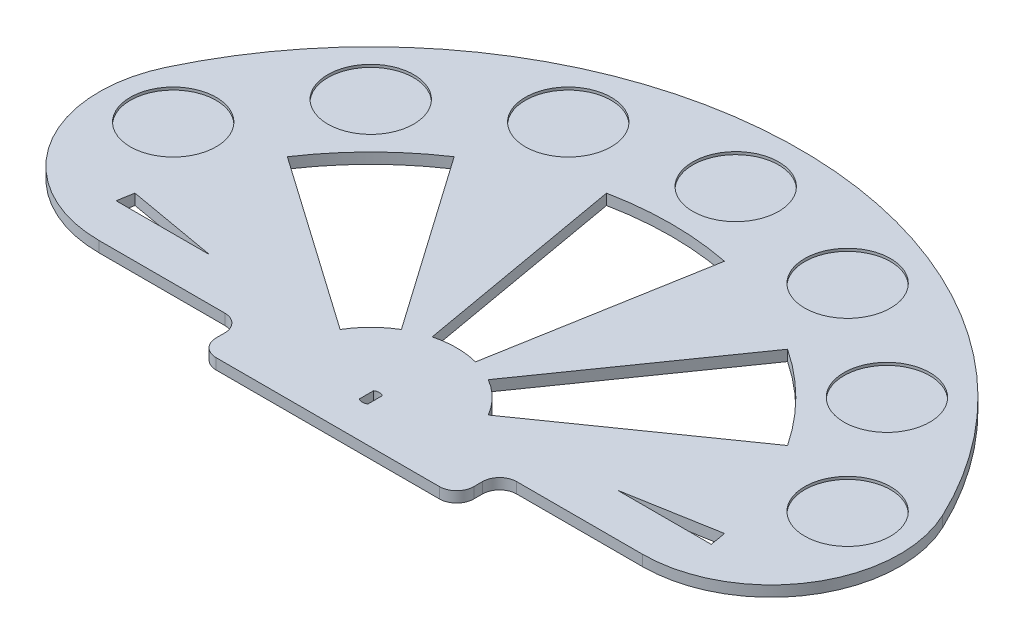
SolidWorks part; units mm, degrees
ref_plane "Front Plane" through (0, 0, 0) normal (0, 0, 1) x (1, 0, 0)
ref_plane "Top Plane" through (0, 0, 0) normal (0, 1, 0) x (1, 0, 0)
ref_plane "Right Plane" through (0, 0, 0) normal (1, 0, 0) x (0, 0, -1)
sketch "Sketch1" plane through (0, 0, 0) normal (0, 1, 0) x (1, 0, 0)
  line L0 (-80.3219, 0) -> (-43.18, 0)
  line L1 (43.18, 0) -> (80.3219, 0)
  line L3 (-38.1, -5.08) -> (-38.1, -7.62)
  line L4 (-33.02, -12.7) -> (33.02, -12.7)
  line L5 (38.1, -5.08) -> (38.1, -7.62)
  line L6 (-1.28, 2.1475) -> (-1.28, -2.1475)
  line L7 (1.28, 2.1475) -> (1.28, -2.1475)
  line L8 (-87.9882, 12.7) -> (87.9882, 12.7) construction
  line L11 (0, 88.9) -> (0, 25.4) construction
  line L12 (-17.4437, 87.1718) -> (-6.4069, 24.5787)
  line L13 (17.4437, 87.1718) -> (6.4069, 24.5787)
  line L14 (-11.9253, 55.8753) -> (11.9253, 55.8753) construction
  line L15 (73.9744, 49.3052) -> (21.9101, 12.8494)
  line L16 (49.3052, 73.9744) -> (12.8494, 21.9101)
  line L18 (87.1718, 17.4437) -> (60.2688, 12.7)
  line L25 (-87.1718, 17.4437) -> (-60.2688, 12.7)
  line L27 (-49.3052, 73.9744) -> (-12.8494, 21.9101)
  line L28 (-73.9744, 49.3052) -> (-21.9101, 12.8494)
  line L29 (-73.9744, -49.3052) -> (-21.9101, -12.8494) [skipped]
  line L30 (-49.3052, -73.9744) -> (-12.8494, -21.9101) [skipped]
  line L31 (-17.4437, -87.1718) -> (-6.4069, -24.5787) [skipped]
  line L32 (17.4437, -87.1718) -> (6.4069, -24.5787) [skipped]
  line L33 (49.3052, -73.9744) -> (12.8494, -21.9101) [skipped]
  line L34 (73.9744, -49.3052) -> (21.9101, -12.8494) [skipped]
  line L35 (87.1718, -17.4437) -> (24.5787, -6.4069) [skipped]
  line L36 (-87.1718, -17.4437) -> (-24.5787, -6.4069) [skipped]
  line L37 (-87.9882, 12.7) -> (-60.2688, 12.7)
  line L38 (87.9882, 12.7) -> (60.2688, 12.7)
  arc A0 (114.7455, 54.4286) -> (-114.7455, 54.4286) centre (0, 0) ccw
  arc A1 (-107.95, 0) -> (107.95, 0) centre (0, 0) cw construction
  circle A2 centre (-107.95, 0) radius 12.7 construction
  circle A3 centre (-99.7328, 41.3107) radius 12.7
  circle A4 centre (-76.3322, 76.3322) radius 12.7
  circle A5 centre (-41.3107, 99.7328) radius 12.7
  circle A6 centre (0, 107.95) radius 12.7
  circle A7 centre (41.3107, 99.7328) radius 12.7
  circle A8 centre (76.3322, 76.3322) radius 12.7
  circle A9 centre (99.7328, 41.3107) radius 12.7
  circle A10 centre (107.95, 0) radius 12.7 construction
  arc A11 (-80.3219, 0) -> (-114.7455, 54.4286) centre (-80.3219, 38.1) cw
  arc A12 (80.3219, 0) -> (114.7455, 54.4286) centre (80.3219, 38.1) ccw
  arc A13 (38.1, -5.08) -> (43.18, 0) centre (43.18, -5.08) cw
  arc A14 (38.1, -7.62) -> (33.02, -12.7) centre (33.02, -7.62) cw
  arc A15 (-38.1, -7.62) -> (-33.02, -12.7) centre (-33.02, -7.62) ccw
  arc A16 (-38.1, -5.08) -> (-43.18, 0) centre (-43.18, -5.08) ccw
  arc A17 (-1.28, -2.1475) -> (1.28, -2.1475) centre (0, 0) ccw
  arc A18 (1.28, 2.1475) -> (-1.28, 2.1475) centre (0, 0) ccw
  arc A19 (88.8946, 0.977) -> (-88.8946, 0.977) centre (0, 0) ccw construction
  arc A20 (21.997, 12.7) -> (-21.997, 12.7) centre (0, 0) ccw construction
  circle A23 centre (0, 0) radius 25.4 construction
  arc A24 (-17.4437, 87.1718) -> (17.4437, 87.1718) centre (0, 0) cw
  arc A25 (-6.4069, 24.5787) -> (6.4069, 24.5787) centre (0, 0) cw
  arc A26 (49.3052, 73.9744) -> (73.9744, 49.3052) centre (0, 0) cw
  arc A27 (12.8494, 21.9101) -> (21.9101, 12.8494) centre (0, 0) cw
  arc A38 (-73.9744, 49.3052) -> (-49.3052, 73.9744) centre (0, 0) cw
  arc A39 (-21.9101, 12.8494) -> (-12.8494, 21.9101) centre (0, 0) cw
  arc A40 (-12.8494, -21.9101) -> (-21.9101, -12.8494) centre (0, 0) cw [skipped]
  arc A41 (-49.3052, -73.9744) -> (-73.9744, -49.3052) centre (0, 0) cw [skipped]
  arc A42 (6.4069, -24.5787) -> (-6.4069, -24.5787) centre (0, 0) cw [skipped]
  arc A43 (17.4437, -87.1718) -> (-17.4437, -87.1718) centre (0, 0) cw [skipped]
  arc A44 (21.9101, -12.8494) -> (12.8494, -21.9101) centre (0, 0) cw [skipped]
  arc A45 (73.9744, -49.3052) -> (49.3052, -73.9744) centre (0, 0) cw [skipped]
  arc A46 (24.5787, 6.4069) -> (24.5787, -6.4069) centre (0, 0) cw [skipped]
  arc A47 (-87.1718, -17.4437) -> (-87.1718, 17.4437) centre (0, 0) cw [skipped]
  arc A48 (-24.5787, -6.4069) -> (-24.5787, 6.4069) centre (0, 0) cw [skipped]
  arc A49 (87.1718, 17.4437) -> (87.1718, -17.4437) centre (0, 0) cw [skipped]
  arc A50 (-87.9882, 12.7) -> (-87.1718, 17.4437) centre (0, 0) cw
  arc A51 (87.9882, 12.7) -> (87.1718, 17.4437) centre (0, 0) ccw
  point P5 (0, 0)
  point P25 (0, 0)
  point P29 (-127, 0)
  point P32 (127, 0)
  point P38 (38.1, 0)
  point P41 (38.1, -12.7)
  point P44 (-38.1, -12.7)
  point P94 (0, 0)
  dimension "D1" = 254
  dimension "D2" = 76.2
  dimension "D3" = 38.1
  dimension "D5" = 38.1
  dimension "D8" = 5.08
  dimension "D9" = 5
  dimension "D11" = 19.05
  dimension "D13" = 50.8
  dimension "D6" = 12.7
  dimension "D7" = 38.1
  dimension "D10" = 2.56
  dimension "D12" = 12.7
  dimension "D16" = 8
  dimension "D4" = 9
extrude "Boss-Extrude1" add sketch "Sketch1" along normal blind 3.175 contours A3 | A16 L3 A15 L4 A14 L5 A13 L1 A12 A0 A11 L0 A51 L38 L18 A39 L28 A38 L27 A27 L16 A26 L15 A25 L12 A24 L13 A18 L7 A17 L6 A9 A8 A7 A6 A5 A4 A3 | A5 | A4 | A6 | A7 | A8 | A9 region at (-84.3246, 0, -2.9771) region at (-99.7328, 0, -41.3107) region at (-76.3322, 0, -76.3322) region at (-41.3107, 0, -99.7328) region at (0, 0, -107.95) region at (41.3107, 0, -99.7328) region at (76.3322, 0, -76.3322) region at (99.7328, 0, -41.3107)
extrude "Cut-Extrude4" cut sketch "Sketch1<4>" against normal blind 0.7937 from offset 3.175 contours A5 | A3 | A4 | A6 | A7 | A8 | A9 region at (-41.3107, 0, -99.7328)
sketch "Sketch1<4>" plane through (0, 0, 0) normal (0, 1, 0) x (1, 0, 0) same geometry as "Sketch1"
